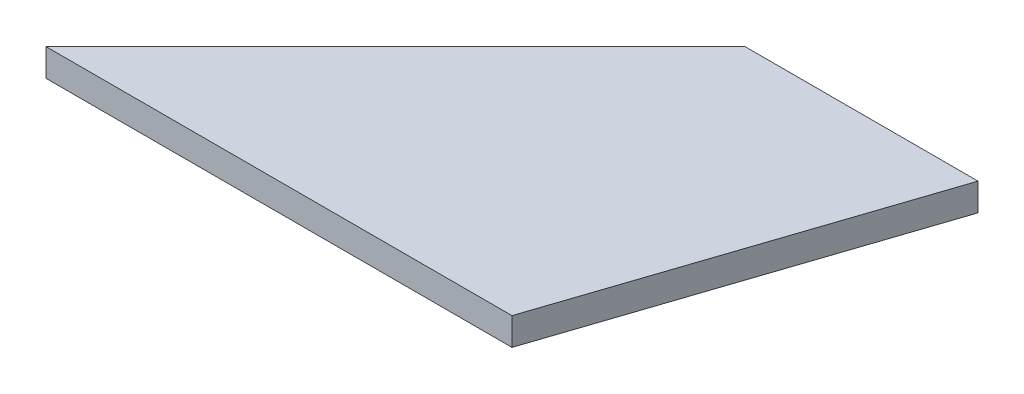
SolidWorks part; units mm, degrees
ref_plane "Front Plane" through (0, 0, 0) normal (0, 0, 1) x (1, 0, 0)
ref_plane "Top Plane" through (0, 0, 0) normal (0, 1, 0) x (1, 0, 0)
ref_plane "Right Plane" through (0, 0, 0) normal (1, 0, 0) x (0, 0, -1)
sketch "Sketch1" plane through (0, 0, 0) normal (0, 1, 0) x (1, 0, 0)
  line L0 (0, 0) -> (50.8, 0)
  line L1 (0, 0) -> (38.1, 38.1)
  line L2 (38.1, 38.1) -> (63.5, 38.1)
  line L3 (63.5, 38.1) -> (50.8, 0)
  dimension "D1" = 38.1
  dimension "D2" = 38.1
extrude "Boss-Extrude1" add sketch "Sketch1" along normal blind 3 contours L3 L0 L1 L2
